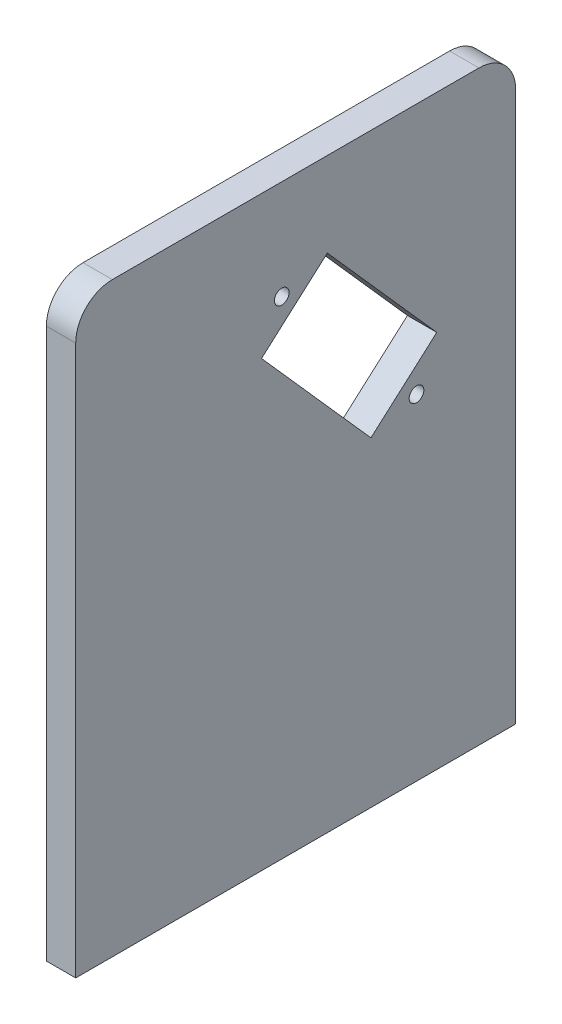
SolidWorks part; units mm, degrees
ref_plane "Front Plane" through (0, 0, 0) normal (0, 0, 1) x (1, 0, 0)
ref_plane "Top Plane" through (0, 0, 0) normal (0, 1, 0) x (1, 0, 0)
ref_plane "Right Plane" through (0, 0, 0) normal (1, 0, 0) x (0, 0, -1)
sketch "Sketch1" plane through (0, 0, 0) normal (0, 1, 0) x (1, 0, 0)
  line L0 (-50.7713, 34.2125) -> (-46.7713, 34.2125)
  line L7 (-46.7713, 34.2125) -> (-46.7713, -25.7875)
  line L8 (-46.7713, -25.7875) -> (-50.7713, -25.7875)
  line L17 (-50.7713, 34.2125) -> (-50.7713, -25.7875)
  dimension "D5" = 4
extrude "Boss-Extrude1" add sketch "Sketch1" along normal blind 3 contours L0 L7 L8 | L8 L7 L0 region at (-48.7713, 0, -4.2125)
extrude "Boss-Extrude2" add sketch "Sketch1<3>" along normal blind 70
sketch "Sketch1<3>" plane through (0, 0, 0) normal (0, 1, 0) x (1, 0, 0) same geometry as "Sketch1"
extrude "Boss-Extrude3" add sketch "Sketch1<4>" along normal blind 70 rebuild error yes
sketch "Sketch1<4>" plane through (0, 0, 0) normal (0, 1, 0) x (1, 0, 0) same geometry as "Sketch1"
sketch "Sketch5" plane through (-50.7713, 0, 0) normal (-1, 0, 0) x (0, 0, 1)
  line L0 (-8.0225, 70) -> (-8.0225, 0) construction
  line L5 (-34.2125, 70) -> (-34.2125, 3) construction
  circle A0 centre (-8.0225, 60) radius 4
  dimension "D1" = 60
  dimension "D3" = 8
  dimension "D2" = 26.19
extrude "Cut-Extrude4" cut sketch "Sketch5" against normal blind 10
sketch "Sketch6" plane through (0, 3, 0) normal (0, 1, 0) x (1, 0, 0)
  line L0 (-50.7876, 44.2125) -> (49.2124, 44.2125) construction
  line L3 (-50.7876, -35.7875) -> (49.2124, -35.7875) construction
  line L8 (-50.7713, -40.7875) -> (39.2287, -40.7875) construction
  line L9 (-50.7713, 49.2125) -> (39.2287, 49.2125) construction
  circle A0 centre (-45.7876, -35.7875) radius 2.5
  circle A1 centre (-45.7876, 44.2125) radius 2.5
  circle A2 centre (43.7185, 44.2125) radius 2.5
  circle A3 centre (43.7185, -35.7875) radius 2.5
  dimension "D1" = 5
  dimension "D2" = 5
  dimension "D3" = 5
  dimension "D4" = 5
extrude "Cut-Extrude5" cut sketch "Sketch6" against normal blind 10 rebuild error yes
extrude "Boss-Extrude4" add sketch "Sketch1<5>" along normal blind 80 contours L7 L8 L17 L0
sketch "Sketch1<5>" plane through (0, 0, 0) normal (0, 1, 0) x (1, 0, 0) same geometry as "Sketch1"
extrude "Cut-Extrude6" cut sketch "Sketch5<2>" against normal blind 10
sketch "Sketch5<2>" plane through (-50.7713, 0, 0) normal (-1, 0, 0) x (0, 0, 1) same geometry as "Sketch5"
fillet "Fillet1" radius 3 rebuild error yes
fillet "Fillet2" radius 5 2 edges at (-48.7713, 80, -34.2125) (-48.7713, 80, 25.7875)
fillet "Fillet3" radius 4 rebuild error yes
sketch "Sketch7" plane through (39.2287, 0, 0) normal (1, 0, 0) x (0, 0, -1)
  line L0 (-30.7875, -10) -> (39.2125, -10) construction
  line L1 (-30.7875, 65) -> (-30.7875, 3) construction
  line L2 (39.2125, 65) -> (39.2125, 3) construction
  line L3 (-37.7875, 0) -> (46.2125, 0) construction
  circle A0 centre (27.4823, -10) radius 2.5
  dimension "D1" = 10
extrude "Cut-Extrude7" cut sketch "Sketch7" against normal blind 10 rebuild error yes
sketch "Sketch8" plane through (39.2287, 0, 0) normal (1, 0, 0) x (0, 0, -1)
  line L0 (39.2125, 20) -> (-30.7875, 20) construction
  line L1 (39.2125, 65) -> (39.2125, 3) construction
  line L2 (-30.7875, 65) -> (-30.7875, 3) construction
  line L3 (26.9146, 20) -> (8.0207, 38.8939) construction
  circle A0 centre (8.0207, 38.8939) radius 2.5
  dimension "D3" = 5
  dimension "D1" = 26.72
  dimension "D2" = 45
extrude "Cut-Extrude8" cut sketch "Sketch8" against normal blind 10 rebuild error yes
sketch "Sketch9" plane through (39.2287, 0, 0) normal (1, 0, 0) x (0, 0, -1)
  circle A0 centre (8.0207, 38.8939) radius 3.5
  dimension "D1" = 7
extrude "Cut-Extrude9" cut sketch "Sketch9" against normal up to surface (67.5 mm away) rebuild error yes
sketch "Sketch26" plane through (0, 3, 0) normal (0, 1, 0) x (1, 0, 0)
  line L0 (39.2287, 39.2125) -> (39.2287, 46.2125) construction
  line L1 (39.2287, -37.7875) -> (39.2287, -30.7875) construction
  circle A0 centre (34.2287, 44.2125) radius 2.5
  circle A2 centre (34.2287, -36.0634) radius 2.5
  dimension "D1" = 5
  dimension "D2" = 5
  dimension "D3" = 5
  dimension "D4" = 5
extrude "Cut-Extrude11" cut sketch "Sketch26" against normal blind 10 contours A2 | A0 rebuild error yes
sketch "Sketch27" plane through (0, 3, 0) normal (0, 1, 0) x (1, 0, 0)
  line L0 (-49.8926, 48.3339) -> (38.35, -39.9088) construction
  line L1 (38.35, 48.3339) -> (-49.8926, -39.9088) construction
  line L2 (7.7287, 4.2125) -> (-19.2713, 4.2125) construction
  line L3 (7.7287, 3.4625) -> (-19.2713, 3.4625)
  line L4 (7.7287, 4.9625) -> (-19.2713, 4.9625)
  line L5 (0.9787, -7.4788) -> (-12.5213, 15.9039) construction
  line L6 (0.3292, -7.8538) -> (-13.1708, 15.5289)
  line L7 (1.6282, -7.1038) -> (-11.8718, 16.2789)
  line L8 (-12.5213, -7.4788) -> (0.9787, 15.9039) construction
  line L9 (-13.1708, -7.1038) -> (0.3292, 16.2789)
  line L10 (-11.8718, -7.8538) -> (1.6282, 15.5289)
  line L11 (-19.2713, 4.2125) -> (7.7287, 4.2125) construction
  line L12 (-19.2713, 4.9625) -> (7.7287, 4.9625)
  line L13 (-19.2713, 3.4625) -> (7.7287, 3.4625)
  line L14 (-12.5213, 15.9039) -> (0.9787, -7.4788) construction
  line L15 (-11.8718, 16.2789) -> (1.6282, -7.1038)
  line L16 (-13.1708, 15.5289) -> (0.3292, -7.8538)
  line L17 (0.9787, 15.9039) -> (-12.5213, -7.4788) construction
  line L18 (1.6282, 15.5289) -> (-11.8718, -7.8538)
  line L19 (0.3292, 16.2789) -> (-13.1708, -7.1038)
  arc A0 (-47.7713, 49.2125) -> (-50.7713, 46.2125) centre (-47.7713, 46.2125) ccw construction
  arc A1 (36.2287, -40.7875) -> (39.2287, -37.7875) centre (36.2287, -37.7875) ccw construction
  arc A2 (39.2287, 46.2125) -> (36.2287, 49.2125) centre (36.2287, 46.2125) ccw construction
  arc A3 (-50.7713, -37.7875) -> (-47.7713, -40.7875) centre (-47.7713, -37.7875) ccw construction
  arc A4 (7.7287, 3.4625) -> (7.7287, 4.9625) centre (7.7287, 4.2125) ccw
  arc A5 (-19.2713, 4.9625) -> (-19.2713, 3.4625) centre (-19.2713, 4.2125) ccw
  circle A9 centre (-5.7713, 4.2125) radius 5.375
  arc A10 (0.3292, -7.8538) -> (1.6282, -7.1038) centre (0.9787, -7.4788) ccw
  arc A11 (-11.8718, 16.2789) -> (-13.1708, 15.5289) centre (-12.5213, 15.9039) ccw
  arc A12 (-13.1708, -7.1038) -> (-11.8718, -7.8538) centre (-12.5213, -7.4788) ccw
  arc A13 (1.6282, 15.5289) -> (0.3292, 16.2789) centre (0.9787, 15.9039) ccw
  arc A14 (-19.2713, 4.9625) -> (-19.2713, 3.4625) centre (-19.2713, 4.2125) ccw
  arc A15 (7.7287, 3.4625) -> (7.7287, 4.9625) centre (7.7287, 4.2125) ccw
  arc A16 (-11.8718, 16.2789) -> (-13.1708, 15.5289) centre (-12.5213, 15.9039) ccw
  arc A17 (0.3292, -7.8538) -> (1.6282, -7.1038) centre (0.9787, -7.4788) ccw
  arc A18 (1.6282, 15.5289) -> (0.3292, 16.2789) centre (0.9787, 15.9039) ccw
  arc A19 (-13.1708, -7.1038) -> (-11.8718, -7.8538) centre (-12.5213, -7.4788) ccw
  circle A20 centre (-5.7713, 4.2125) radius 2.75
  point P18 (-5.7713, 4.2125)
  point P30 (-5.7713, 4.2125)
  point P37 (-5.7713, 4.2125)
  point P44 (-5.7713, 4.2125)
  point P51 (-5.7713, 4.2125)
  point P58 (-5.7713, 4.2125)
  point P63 (-5.7713, 4.2125)
  dimension "D1" = 10.75
  dimension "D2" = 0.75
  dimension "D3" = 13.5
  dimension "D4" = 6
extrude "Cut-Extrude14" cut sketch "Sketch27" against normal blind 10 contours L3 A5 L4 A4 | L6 A11 L7 A10 | L10 A13 L9 A12 rebuild error yes
extrude "Cut-Extrude15" cut sketch "Sketch27<7>" against normal blind 10 contours L3 A20 L9 | L6 A20 L4 | L9 A20 L7 | L4 A20 L10 | L7 A20 L3 | L10 A20 L6 rebuild error yes
sketch "Sketch27<7>" plane through (0, 3, 0) normal (0, 1, 0) x (1, 0, 0) same geometry as "Sketch27"
sketch "Sketch28" plane through (-50.7713, 0, 0) normal (-1, 0, 0) x (0, 0, 1)
  line L0 (-23.4588, 51.635) -> (-8.5312, 68.47)
  line L1 (-8.5312, 68.47) -> (0.4475, 60.5086)
  line L2 (0.4475, 60.5086) -> (-14.4801, 43.6736)
  line L3 (-14.4801, 43.6736) -> (-23.4588, 51.635)
  line L4 (-8.0225, 60) -> (-12.6884, 54.7379) construction
  line L5 (-12.6884, 54.7379) -> (-25.2505, 40.5707) construction
  line L6 (-8.0225, 60) -> (2.1094, 71.4266) construction
  circle A0 centre (-8.0225, 60) radius 4 construction
  circle A1 centre (-8.0225, 60) radius 4
  circle A2 centre (-2.3169, 66.4347) radius 1
  circle A3 centre (-20.6944, 45.709) radius 1
  point P8 (-18.9694, 47.6543)
  dimension "D3" = 2
  dimension "D4" = 8.6
  dimension "D5" = 27.7
  dimension "D1" = 22.5
  dimension "D2" = 12
  dimension "D6" = 2.6
extrude "Cut-Extrude16" cut sketch "Sketch28" against normal up to surface (4 mm away) up to face at (-46.7713, 60, -12.0225)
sketch "Sketch29" plane through (39.2287, 0, 0) normal (1, 0, 0) x (0, 0, -1)
  line L8 (8.0207, 38.8939) -> (0.0593, 47.8726) construction
  line L9 (0.0593, 47.8726) -> (37.8759, 5.2239) construction
  line L10 (8.5294, 47.3639) -> (23.457, 30.5289)
  line L11 (23.457, 30.5289) -> (14.4783, 22.5675)
  line L12 (14.4783, 22.5675) -> (-0.4493, 39.4025)
  line L13 (-0.4493, 39.4025) -> (8.5294, 47.3639)
  circle A6 centre (8.0207, 38.8939) radius 3.5 construction
  circle A7 centre (8.0207, 38.8939) radius 3.5
  circle A8 centre (2.3151, 45.3286) radius 1
  circle A9 centre (20.6926, 24.6028) radius 1
  point P4 (4.04, 43.3832)
  point P28 (18.9676, 26.5482)
  dimension "D4" = 2.6
  dimension "D5" = 27.7
  dimension "D6" = 2
  dimension "D7" = 2
  dimension "D2" = 12
  dimension "D3" = 22.5
  dimension "D8" = 8.6
extrude "Cut-Extrude18" cut sketch "Sketch29" against normal up to surface (4 mm away) rebuild error yes
sketch "Sketch31" plane through (0, 3, 0) normal (0, 1, 0) x (1, 0, 0)
  circle A0 centre (-5.7713, 4.2125) radius 5.375
  dimension "D1" = 10.75
extrude "Cut-Extrude19" cut sketch "Sketch31" against normal blind 10 rebuild error yes
